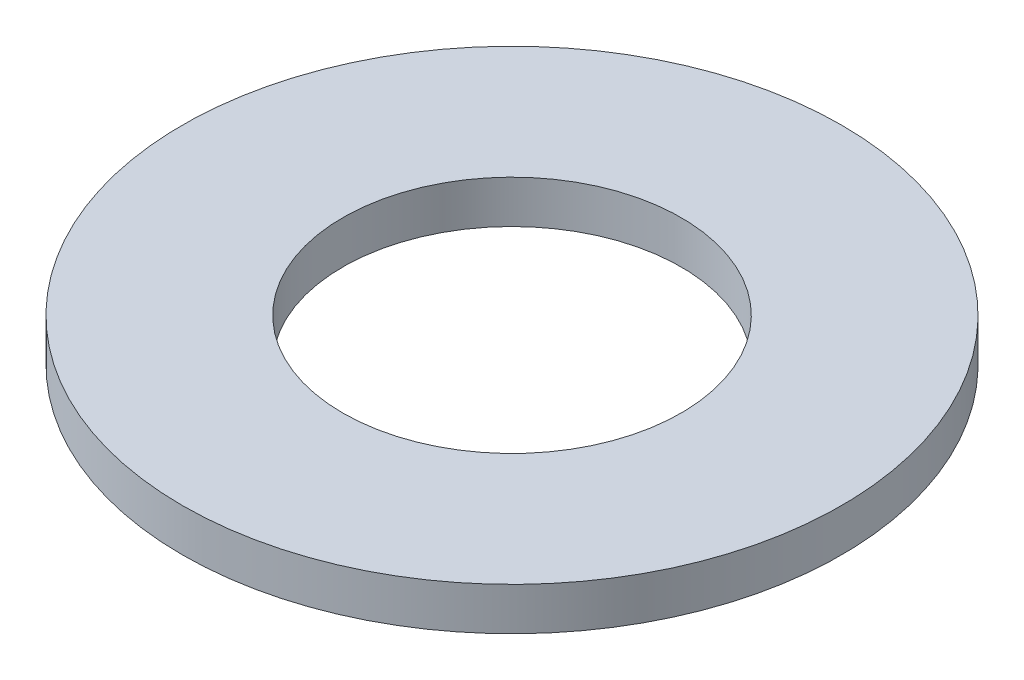
SolidWorks part; units mm, degrees
ref_plane "Front Plane" through (0, 0, 0) normal (0, 0, 1) x (1, 0, 0)
ref_plane "Top Plane" through (0, 0, 0) normal (0, 1, 0) x (1, 0, 0)
ref_plane "Right Plane" through (0, 0, 0) normal (1, 0, 0) x (0, 0, -1)
sketch "Sketch1" plane through (0, 0, 0) normal (0, 1, 0) x (1, 0, 0)
  circle A0 centre (0, 0) radius 92.5
  dimension "FLANGE_OD" = 185
extrude "Boss-Extrude1" add sketch "Sketch1" along normal blind 12
sketch "Sketch2" plane through (0, 0, 0) normal (0, 1, 0) x (1, 0, 0)
  circle A0 centre (0, 0) radius 47.5
  dimension "BORE_D" = 95
extrude "Cut-Extrude1" cut sketch "Sketch2" along normal through all
sketch "Sketch3" plane through (0, 12, 0) normal (0, 1, 0) x (1, 0, 0)
  circle A0 centre (0, 0) radius 28.5316 construction
  circle A1 centre (-28.5316, 0) radius 4.8276
  dimension "BOLT_D" = 9.6552
  dimension "BOLT_PCD" = 57.0632
extrude "Cut-Extrude2" cut sketch "Sketch3" against normal blind 9.8809 rebuild error yes
pattern_circular "CirPattern1" count 6 over 360 rebuild error yes
